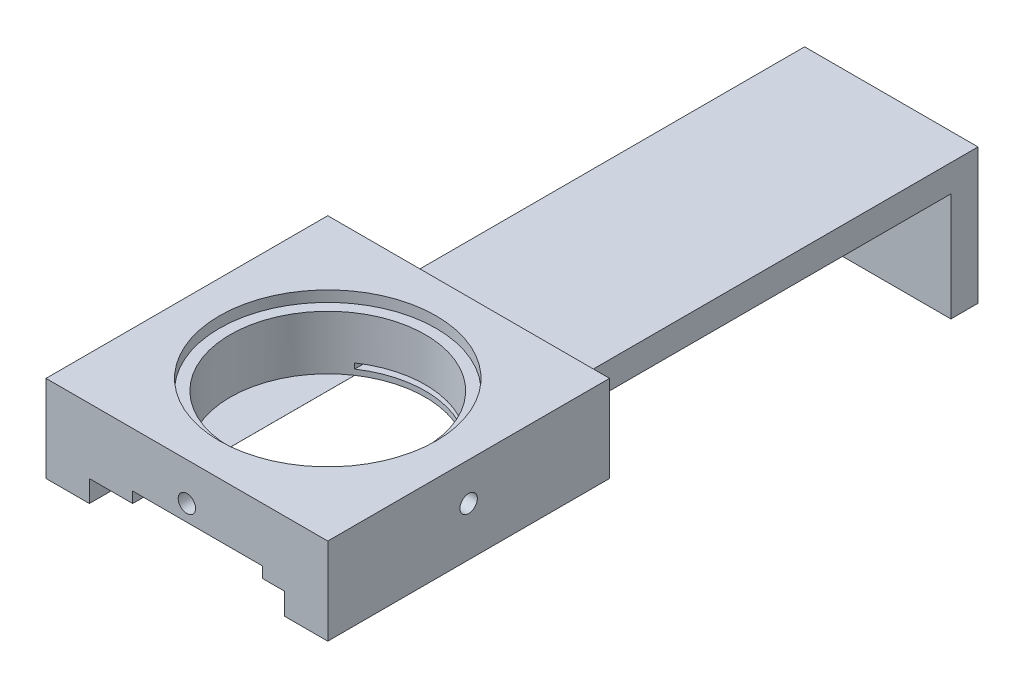
SolidWorks part; units mm, degrees
note: '?' marks a value the reader was unsure of.
material "1060 Alloy"
ref_plane "Front Plane" through (0, 0, 0) normal (0, 0, 1) x (1, 0, 0)
ref_plane "Top Plane" through (0, 0, 0) normal (0, 1, 0) x (1, 0, 0)
ref_plane "Right Plane" through (0, 0, 0) normal (1, 0, 0) x (0, 0, -1)
sketch "Sketch1" plane through (0, 0, 0) normal (0, 1, 0) x (1, 0, 0)
  line L0 (-22.225, 41.275) -> (-41.275, 41.275)
  line L1 (41.275, -41.275) -> (-41.275, -41.275)
  line L2 (41.275, -41.275) -> (41.275, 41.275)
  line L3 (41.275, 41.275) -> (28.575, 41.275)
  line L4 (-41.275, -41.275) -> (-41.275, 41.275)
  line L5 (41.275, -41.275) -> (-41.275, 41.275) construction
  line L6 (41.275, 41.275) -> (-41.275, -41.275) construction
  line L8 (-22.225, 41.275) -> (-22.225, 161.925)
  line L9 (-22.225, 161.925) -> (28.575, 161.925)
  line L10 (28.575, 41.275) -> (28.575, 161.925)
  point P0 (0, 0)
  dimension "D1" = 82.55
  dimension "D2" = 82.55
  dimension "D3" = 50.8
  dimension "D4" = 12.7
  dimension "D5" = 203.2
extrude "Boss-Extrude1" add sketch "Sketch1" against normal blind 7.9375
sketch "Sketch2" plane through (0, -7.9375, 0) normal (0, -1, 0) x (1, 0, 0)
  line L0 (28.575, -41.275) -> (28.575, -161.925) construction
  line L1 (-22.225, -161.925) -> (28.575, -161.925)
  line L2 (-22.225, -161.925) -> (-22.225, -153.9875)
  line L3 (-22.225, -153.9875) -> (28.575, -153.9875)
  line L4 (28.575, -161.925) -> (28.575, -153.9875)
  dimension "D1" = 7.9375
extrude "Boss-Extrude2" add sketch "Sketch2" along normal blind 31.75
sketch "Sketch8" plane through (0, 0, 0) normal (0, 1, 0) x (1, 0, 0)
  line L1 (-41.275, -41.275) -> (41.275, -41.275)
  line L2 (-41.275, -41.275) -> (-41.275, 41.275)
  line L3 (-41.275, 41.275) -> (41.275, 41.275)
  line L4 (41.275, -41.275) -> (41.275, 41.275)
extrude "Boss-Extrude6" add sketch "Sketch8" along normal blind 7.9375
sketch "Sketch3" plane through (0, -7.9375, 0) normal (0, -1, 0) x (1, 0, 0)
  line L0 (-22.225, -41.275) -> (-41.275, -41.275) construction
  line L1 (-41.275, 41.275) -> (-29.0692, 41.275)
  line L2 (-41.275, 41.275) -> (-41.275, -41.275)
  line L3 (-41.275, -41.275) -> (-29.0692, -41.275)
  line L4 (-29.0692, 41.275) -> (-29.0692, -41.275)
  line L6 (41.275, 41.275) -> (28.575, 41.275)
  line L7 (41.275, 41.275) -> (41.275, -41.275)
  line L8 (41.275, -41.275) -> (28.575, -41.275)
  line L9 (28.575, 41.275) -> (28.575, -41.275)
extrude "Boss-Extrude3" [suppressed] add sketch "Sketch3" along normal blind 7.9375
sketch "Sketch4" plane through (0, 0, 0) normal (0, 1, 0) x (1, 0, 0)
  circle A0 centre (0, 0) radius 6.35
  dimension "D1" = 12.7
extrude "Cut-Extrude1" [suppressed] cut sketch "Sketch4" against normal through all
sketch "Sketch5" [suppressed] plane through (0, -7.9375, 0) normal (0, -1, 0) x (1, 0, 0)
  line L1 (-29.0692, 41.275) -> (-16.3692, 41.275)
  line L2 (-29.0692, 41.275) -> (-29.0692, -41.275)
  line L3 (-29.0692, -41.275) -> (-16.3692, -41.275)
  line L4 (-16.3692, 41.275) -> (-16.3692, -41.275)
  line L5 (28.575, 41.275) -> (22.225, 41.275)
  line L6 (28.575, 41.275) -> (28.575, -41.275)
  line L7 (28.575, -41.275) -> (22.225, -41.275)
  line L8 (22.225, 41.275) -> (22.225, -41.275)
  dimension "D1" = 12.7
  dimension "D2" = 82.55
  dimension "D3" = 6.35
  dimension "D4" = 82.55
extrude "Boss-Extrude4" [suppressed] add sketch "Sketch5" along normal blind 1.5875
sketch "Sketch6" plane through (0, 0, 0) normal (0, 1, 0) x (1, 0, 0)
  circle A0 centre (0, 0) radius 28.575
  circle A1 centre (0, 0) radius 38.1
  dimension "D1" = 57.15
  dimension "D2" = 76.2
extrude "Boss-Extrude5" [suppressed] add sketch "Sketch6" along normal blind 1.5875
sketch "Sketch10" plane through (0, 7.9375, 0) normal (0, 1, 0) x (1, 0, 0)
  circle A0 centre (0, 0) radius 6.35
  dimension "D1" = 12.7
extrude "Center Hole" cut sketch "Sketch10" against normal up to surface (15.875 mm away) up to face at (1.5875, -7.9375, -48.8156)
sketch "Sketch12" plane through (0, -7.9375, 0) normal (0, -1, 0) x (1, 0, 0)
  line L1 (-41.275, 41.275) -> (-28.575, 41.275)
  line L2 (-41.275, 41.275) -> (-41.275, -41.275)
  line L3 (-41.275, -41.275) -> (-28.575, -41.275)
  line L4 (-28.575, 41.275) -> (-28.575, -41.275)
  line L6 (41.275, 41.275) -> (28.575, 41.275)
  line L7 (41.275, 41.275) -> (41.275, -41.275)
  line L8 (41.275, -41.275) -> (28.575, -41.275)
  line L9 (28.575, 41.275) -> (28.575, -41.275)
  dimension "D1" = 82.55
  dimension "D2" = 82.55
  dimension "D3" = 12.7
  dimension "D4" = 12.7
extrude "Clamp Pad" add sketch "Sketch12" along normal blind 9.525
sketch "Sketch13" plane through (0, -7.9375, 0) normal (0, -1, 0) x (1, 0, 0)
  line L1 (-28.575, 41.275) -> (-15.875, 41.275)
  line L2 (-28.575, 41.275) -> (-28.575, -41.275)
  line L3 (-28.575, -41.275) -> (-15.875, -41.275)
  line L4 (-15.875, 41.275) -> (-15.875, -41.275)
  line L5 (-15.875, -41.275) -> (22.225, -41.275) construction
  line L6 (28.575, 41.275) -> (22.225, 41.275)
  line L7 (28.575, 41.275) -> (28.575, -41.275)
  line L8 (28.575, -41.275) -> (22.225, -41.275)
  line L9 (22.225, 41.275) -> (22.225, -41.275)
  line L10 (-41.275, -41.275) -> (-28.575, -41.275) construction
  dimension "D1" = 12.7
  dimension "D2" = 6.35
extrude "Wear Pad" add sketch "Sketch13" along normal blind 3.175
sketch "Sketch14" plane through (0, 7.9375, 0) normal (0, 1, 0) x (1, 0, 0)
  line L1 (-41.275, 41.275) -> (41.275, 41.275)
  line L2 (-41.275, 41.275) -> (-41.275, -41.275)
  line L3 (-41.275, -41.275) -> (41.275, -41.275)
  line L4 (41.275, 41.275) -> (41.275, -41.275)
extrude "Boss-Extrude10" add sketch "Sketch14" along normal up to vertex (0.0143 mm away)
sketch "Sketch15" plane through (0, 7.9518, 0) normal (0, 1, 0) x (1, 0, 0)
  circle A0 centre (0, 0) radius 28.575
  dimension "D1" = 57.15
extrude "Cut-Extrude3" cut sketch "Sketch15" against normal blind 19.05
sketch "Sketch11" plane through (0, -11.0982, 0) normal (0, 1, 0) x (1, 0, 0)
  circle A0 centre (0, 0) radius 28.575
  circle A1 centre (0, 0) radius 38.1
  dimension "D1" = 57.15
  dimension "D2" = 76.2
extrude "Boss-Extrude7" add sketch "Sketch11" along normal blind 1.5875
ref_axis "Axis1" through (0, 18.6531, 0) along (0, -1, 0)?
sketch "Sketch24" plane through (0, 7.9518, 0) normal (0, 1, 0) x (1, 0, 0)
  circle A0 centre (0, 0) radius 31.75
  dimension "D1" = 63.5
extrude "Cut-Extrude4" cut sketch "Sketch24" against normal blind 3.175
hole_wizard "1/4-20 Tapped Hole5" positions "Sketch29" profile "Sketch30" tap size "1/4-20" standard "ANSI Inch"
sketch "Sketch29" plane through (0, 0, 41.275) normal (0, 0, 1) x (1, 0, 0)
  line L0 (-41.275, 7.9518) -> (41.275, 7.9518) construction
  line L2 (0, -3.1607) -> (0, 0) construction
  point P0 (0, -3.1607)
  dimension "D1" = 11.1125
sketch "Sketch30" plane through (0, -3.1607, 41.275) normal (1, 0, 0) x (0, -1, 0)
  line L0 (0, 0) -> (0, 12.7)
  line L1 (0, 12.7) -> (2.5527, 12.7)
  line L2 (2.5527, 12.7) -> (2.5527, 0)
  line L5 (2.5527, 0) -> (0, 0)
  line L11 (0, -6.35) -> (0, 107.95) construction
  dimension "Thru Tap Drill Dia." = 5.1054
  dimension "Thru Tap Drill Depth" = 12.7
cosmetic thread "Hole Thread8" parameters "D2"=6.35
hole_wizard "1/4-20 Tapped Hole6" positions "Sketch31" profile "Sketch32" tap size "1/4-20" standard "ANSI Inch"
sketch "Sketch31" plane through (41.275, 0, 0) normal (1, 0, 0) x (0, 0, -1)
  line L0 (-41.275, 7.9518) -> (41.275, 7.9518) construction
  line L1 (0, -3.1607) -> (0, 0) construction
  point P0 (0, -3.1607)
  dimension "D1" = 11.1125
sketch "Sketch32" plane through (41.275, -3.1607, 0) normal (0, 1, 0) x (0, 0, -1)
  line L0 (0, 0) -> (0, 12.7)
  line L1 (0, 12.7) -> (2.5527, 12.7)
  line L2 (2.5527, 12.7) -> (2.5527, 0)
  line L5 (2.5527, 0) -> (0, 0)
  line L11 (0, -6.35) -> (0, 107.95) construction
  dimension "Thru Tap Drill Dia." = 5.1054
  dimension "Thru Tap Drill Depth" = 12.7
cosmetic thread "Hole Thread9" parameters "D2"=6.35
hole_wizard "1/4-20 Tapped Hole7" positions "Sketch33" profile "Sketch34" tap size "1/4-20" standard "ANSI Inch"
sketch "Sketch33" plane through (0, -17.4625, 0) normal (0, -1, 0) x (-1, 0, 0)
  point P0 (33.3375, 19.05)
  point P3 (33.3375, -19.05)
sketch "Sketch34" plane through (-33.3375, -17.4625, -19.05) normal (1, 0, 0) x (0, 0, -1)
  line L0 (0, 0) -> (0, 18.0438)
  line L1 (0, 18.0438) -> (2.5527, 16.51)
  line L2 (2.5527, 16.51) -> (2.5527, 0)
  line L5 (2.5527, 0) -> (0, 0)
  line L10 (0, 18.0438) -> (-2.5527, 16.51) construction
  line L11 (0, -6.35) -> (0, 107.95) construction
  dimension "Tap Drill Dia." = 5.1054
  dimension "Tap Drill Depth" = 16.51
  dimension "Drill Angle" = 118
cosmetic thread "Hole Thread10" parameters "D1"=12.7, "D2"=6.35
cosmetic thread "Hole Thread11" parameters "D1"=12.7, "D2"=6.35
hole_wizard "1/4-20 Tapped Hole8" positions "Sketch35" profile "Sketch36" tap size "1/4-20" standard "ANSI Inch"
sketch "Sketch35" plane through (0, -17.4625, 0) normal (0, -1, 0) x (-1, 0, 0)
  point P0 (-33.3375, 19.05)
  point P3 (-33.3375, -19.05)
cosmetic thread "Hole Thread12" parameters "D1"=12.7, "D2"=6.35
cosmetic thread "Hole Thread13" parameters "D1"=12.7, "D2"=6.35
sketch "Sketch36" plane through (33.3375, -17.4625, -19.05) normal (1, 0, 0) x (0, 0, -1)
  line L0 (0, 0) -> (0, 18.0438)
  line L1 (0, 18.0438) -> (2.5527, 16.51)
  line L2 (2.5527, 16.51) -> (2.5527, 0)
  line L5 (2.5527, 0) -> (0, 0)
  line L10 (0, 18.0438) -> (-2.5527, 16.51) construction
  line L11 (0, -6.35) -> (0, 107.95) construction
  dimension "Tap Drill Dia." = 5.1054
  dimension "Tap Drill Depth" = 16.51
  dimension "Drill Angle" = 118
